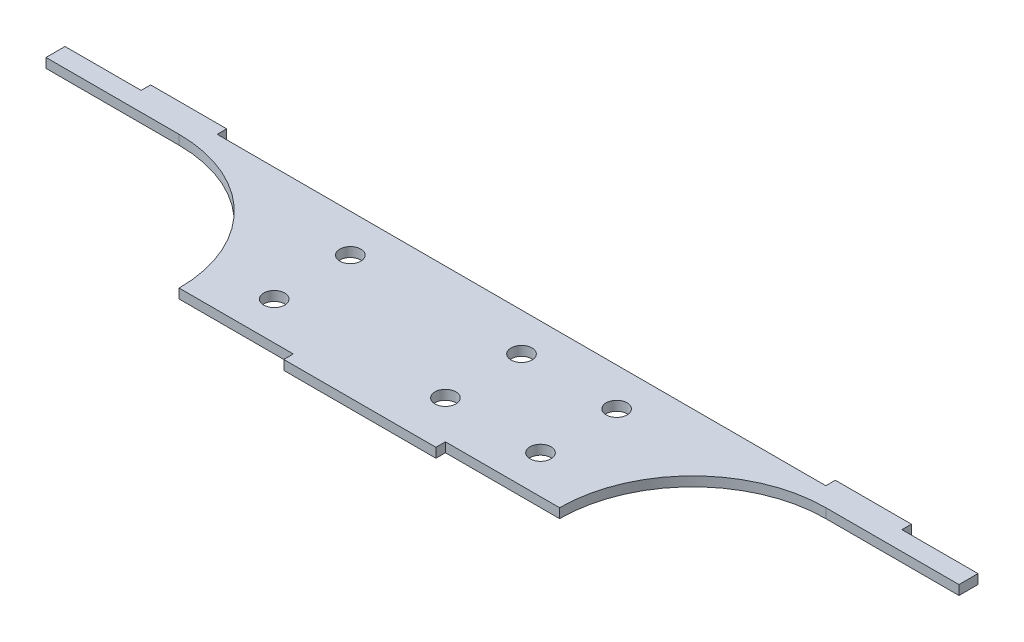
SolidWorks part; units mm, degrees
ref_plane "Front Plane" through (0, 0, 0) normal (0, 0, 1) x (1, 0, 0)
ref_plane "Top Plane" through (0, 0, 0) normal (0, 1, 0) x (1, 0, 0)
ref_plane "Right Plane" through (0, 0, 0) normal (1, 0, 0) x (0, 0, -1)
sketch "Sketch1" plane through (0, 0, 0) normal (0, 1, 0) x (1, 0, 0)
  line L0 (-107.95, 19.05) -> (-152.4, 19.05)
  line L1 (-152.4, -25.4) -> (152.4, -25.4)
  line L2 (-152.4, -25.4) -> (-152.4, 25.4)
  line L3 (-152.4, 25.4) -> (152.4, 25.4)
  line L4 (152.4, -25.4) -> (152.4, 25.4)
  line L5 (-152.4, -25.4) -> (152.4, 25.4) construction
  line L6 (-152.4, 25.4) -> (152.4, -25.4) construction
  line L7 (152.4, 19.05) -> (107.95, 19.05)
  line L8 (44.45, 12.7) -> (12.7, 12.7) construction
  line L9 (-44.45, -12.7) -> (44.45, -12.7) construction
  line L10 (-44.45, -12.7) -> (-44.45, 12.7) construction
  line L11 (-44.45, 12.7) -> (44.45, 12.7) construction
  line L12 (44.45, -12.7) -> (44.45, 12.7) construction
  line L13 (-44.45, -12.7) -> (44.45, 12.7) construction
  line L14 (-44.45, 12.7) -> (44.45, -12.7) construction
  line L15 (127, 28.575) -> (152.4, 28.575) construction
  line L16 (-25.4, -25.4) -> (25.4, -25.4)
  line L17 (-25.4, -25.4) -> (-25.4, -28.575)
  line L18 (-25.4, -28.575) -> (25.4, -28.575)
  line L19 (25.4, -25.4) -> (25.4, -28.575)
  line L20 (-127, 28.575) -> (-101.6, 28.575)
  line L21 (-127, 28.575) -> (-127, 25.4)
  line L22 (-127, 25.4) -> (-101.6, 25.4)
  line L23 (-101.6, 28.575) -> (-101.6, 25.4)
  line L24 (101.6, 28.575) -> (127, 28.575)
  line L25 (101.6, 28.575) -> (101.6, 25.4)
  line L26 (101.6, 25.4) -> (127, 25.4)
  line L27 (127, 28.575) -> (127, 25.4)
  line L28 (-127, 28.575) -> (-152.4, 28.575) construction
  arc A0 (-107.95, 19.05) -> (-63.5, -25.4) centre (-107.95, -25.4) cw
  arc A1 (107.95, 19.05) -> (63.5, -25.4) centre (107.95, -25.4) ccw
  circle A2 centre (-44.45, 12.7) radius 3.5
  circle A3 centre (-44.45, -12.7) radius 3.5
  circle A4 centre (44.45, 12.7) radius 3.5
  circle A5 centre (44.45, -12.7) radius 3.5
  circle A6 centre (12.7, 12.7) radius 3.5
  circle A7 centre (12.7, -12.7) radius 3.5
  point P0 (0, 0)
  point P14 (0, 0)
  point P31 (0, -28.575)
  dimension "D4" = 44.45
  dimension "D8" = 7
  dimension "D9" = 7
  dimension "D1" = 50.8
  dimension "D2" = 304.8
  dimension "D3" = 44.45
  dimension "D5" = 88.9
  dimension "D6" = 25.4
  dimension "D7" = 31.75
  dimension "D10" = 3.175
  dimension "D11" = 50.8
  dimension "D12" = 25.4
  dimension "D13" = 3.175
extrude "Boss-Extrude1" add sketch "Sketch1" along normal blind 3.175 contours L0 A0 L1 L4 L3 L2 | L17 L16 L19 L18 | L21 L20 L23 L22 | L25 L24 L27 L26 region at (-0.1192, 0, -4.0045)
